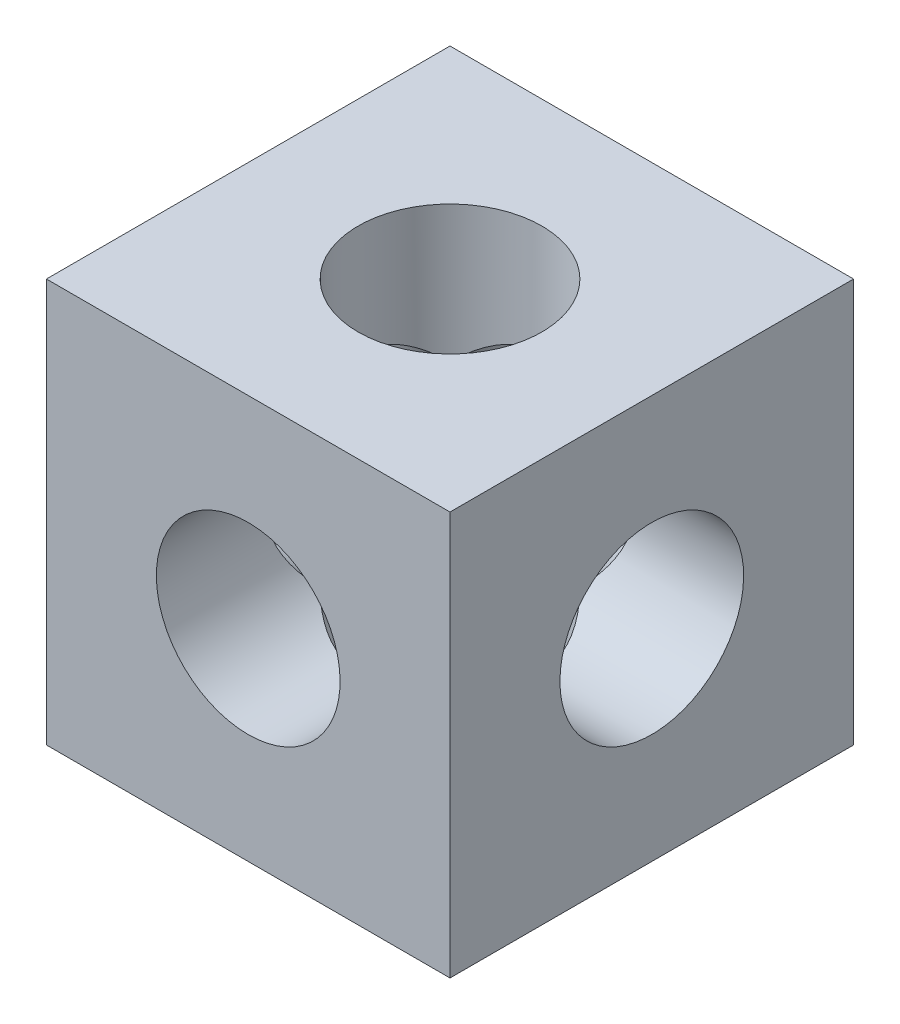
SolidWorks part; units mm, degrees
ref_plane "Front Plane" through (0, 0, 0) normal (0, 0, 1) x (1, 0, 0)
ref_plane "Top Plane" through (0, 0, 0) normal (0, 1, 0) x (1, 0, 0)
ref_plane "Right Plane" through (0, 0, 0) normal (1, 0, 0) x (0, 0, -1)
sketch "Sketch1" plane through (0, 0, 0) normal (0, 1, 0) x (1, 0, 0)
  line L0 (17.4625, 0) -> (17.4625, 34.925) construction
  line L1 (0, 0) -> (34.925, 0)
  line L2 (0, 0) -> (0, 34.925)
  line L3 (0, 34.925) -> (34.925, 34.925)
  line L4 (34.925, 0) -> (34.925, 34.925)
  line L5 (0, 17.4625) -> (34.925, 17.4625) construction
  circle A0 centre (17.4625, 17.4625) radius 7.9502
  dimension "D3" = 15.9004
  dimension "D1" = 34.925
  dimension "D2" = 34.925
extrude "Cube" add sketch "Sketch1" along normal blind 34.925 contours L1 L4 L3 L2 A0 | A0 region at (0.4939, 0, -17.4625) region at (17.4625, 0, -17.4625)
ref_plane "Plane2" through (0, 17.4625, 0) normal (0, 1, 0) x (1, 0, 0)
ref_plane "Plane3" through (17.4625, 0, 0) normal (-1, 0, 0) x (0, 0, 1)
ref_plane "Plane4" through (0, 0, -17.4625) normal (0, 0, -1) x (-1, 0, 0)
ref_axis "Axis2" through (-1.7463, 17.4625, -17.4625) along (1, 0, 0)
ref_axis "Axis3" through (17.4625, 17.4625, 1.7463) along (0, 0, -1)
ref_axis "Axis4" through (17.4625, -1.7463, -17.4625) along (0, 1, 0)
extrude "Cut-Extrude1" cut sketch "Sketch1<3>" along normal through all contours A0
sketch "Sketch1<3>" plane through (0, 0, 0) normal (0, 1, 0) x (1, 0, 0) same geometry as "Sketch1"
pattern_circular "CirPattern2" count 2 every 90 about axis through (-1.7463, 17.4625, -17.4625) along (1, 0, 0) of "Cut-Extrude1"
pattern_circular "CirPattern3" count 2 every 90 about axis through (17.4625, 17.4625, 1.7463) along (0, 0, -1) of "CirPattern2"
